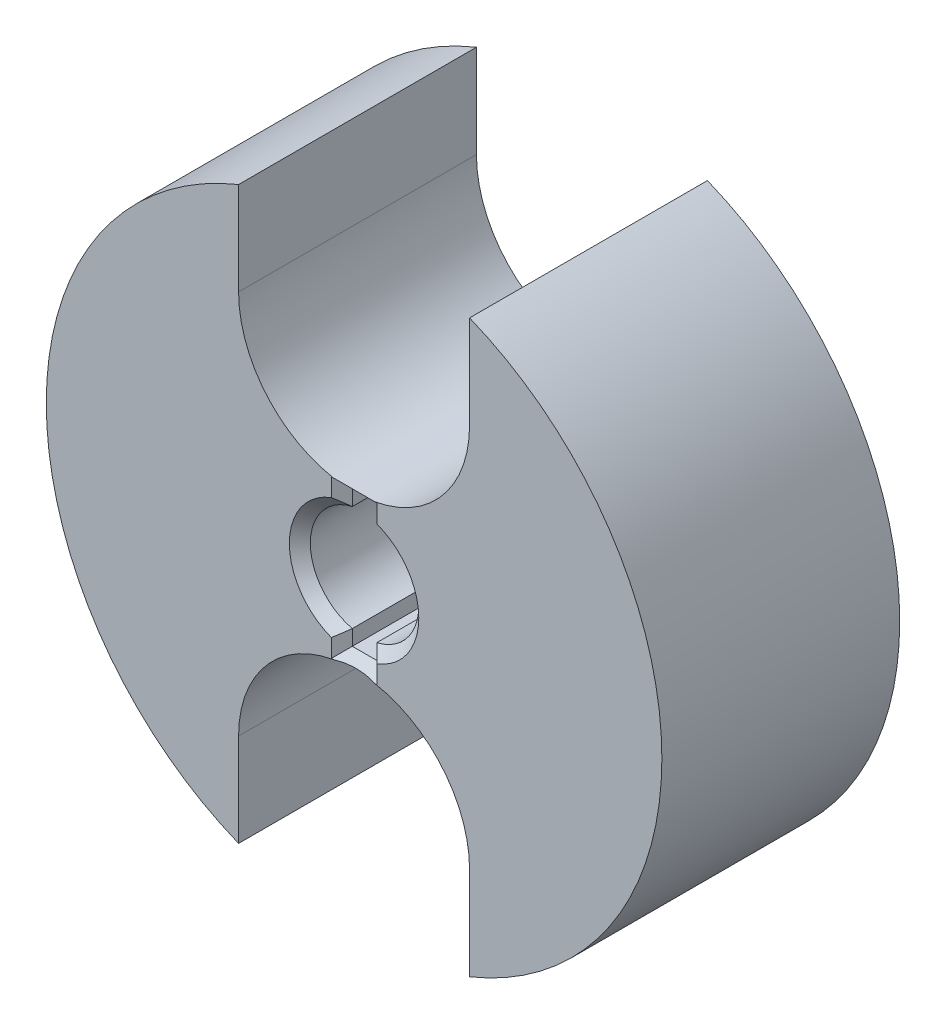
SolidWorks part; units mm, degrees
ref_plane "Front Plane" through (0, 0, 0) normal (0, 0, 1) x (1, 0, 0)
ref_plane "Top Plane" through (0, 0, 0) normal (0, 1, 0) x (1, 0, 0)
ref_plane "Right Plane" through (0, 0, 0) normal (1, 0, 0) x (0, 0, -1)
sketch "Sketch1" plane through (0, 0, 0) normal (0, 0, 1) x (1, 0, 0)
  line L1 (-8.255, 25) -> (8.255, 25)
  line L2 (-8.255, 25) -> (-8.255, -25)
  line L3 (-8.255, -25) -> (8.255, -25)
  line L4 (8.255, 25) -> (8.255, -25)
  line L5 (-8.255, 25) -> (8.255, -25) construction
  line L6 (-8.255, -25) -> (8.255, 25) construction
  line L7 (-0.875, 4.875) -> (0.875, 4.875)
  line L8 (-0.875, 4.875) -> (-0.875, -4.875)
  line L9 (-0.875, -4.875) -> (0.875, -4.875)
  line L10 (0.875, 4.875) -> (0.875, -4.875)
  line L11 (-0.875, 4.875) -> (0.875, -4.875) construction
  line L12 (-0.875, -4.875) -> (0.875, 4.875) construction
  circle A0 centre (0, 0) radius 22
  circle A1 centre (0, 13.745) radius 8.255
  circle A2 centre (0, -13.745) radius 8.255
  circle A3 centre (0, 0) radius 3.875
  dimension "D1" = 44
  dimension "D2" = 16.51
  dimension "D3" = 16.51
  dimension "D6" = 7.75
  dimension "D4" = 16.51
  dimension "D5" = 50
  dimension "D7" = 9.75
  dimension "D8" = 1.75
extrude "Boss-Extrude1" add sketch "Sketch1" along normal blind 17 contours L2 A0 | L4 A0 | A2 L4 A1 L2 A3 L8 L7 L10 L9 region at (-13.9333, 0, 0) region at (13.9333, 0, 0) region at (0, 5.1693, 0)
chamfer "Chamfer1" distance 0.75 angle 45 8 edges at (0.875, -4.325, 0) (0, -4.875, 0) (-0.875, -4.325, 0) (-3.875, 0, 0) (-0.875, 4.325, 0) (0, 4.875, 0) (0.875, 4.325, 0) (3.875, 0, 0)
chamfer "Chamfer2" distance 0.75 angle 45 8 edges at (-0.875, -4.325, 17) (0, -4.875, 17) (0.875, -4.325, 17) (3.875, 0, 17) (0.875, 4.325, 17) (0, 4.875, 17) (-0.875, 4.325, 17) (-3.875, 0, 17)
